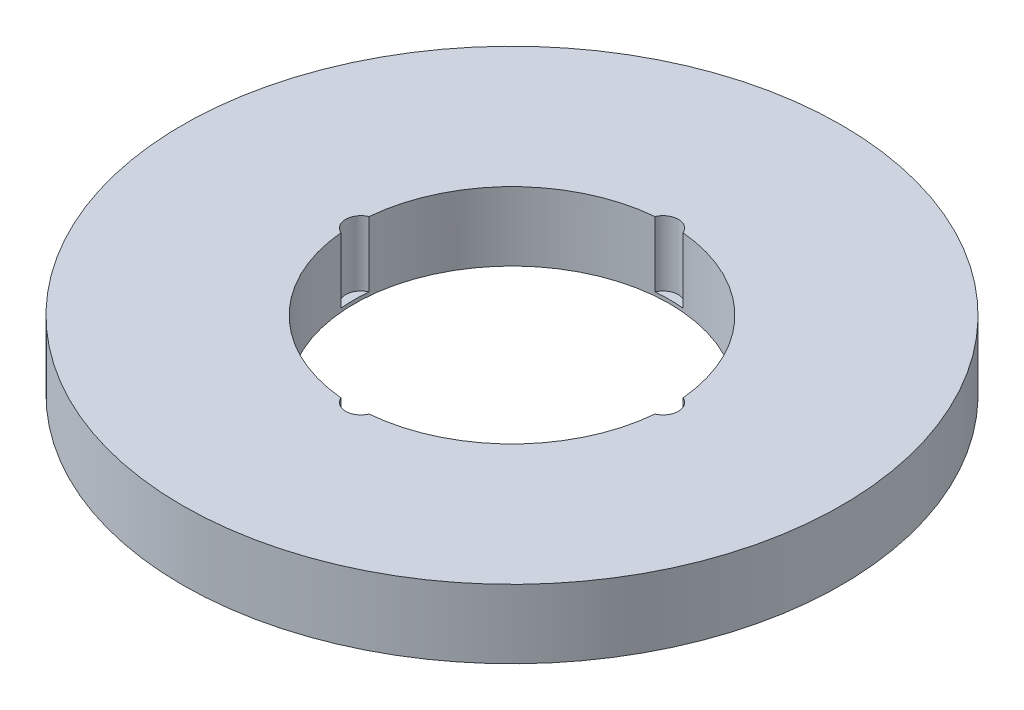
SolidWorks part; units mm, degrees
ref_plane "Front Plane" through (0, 0, 0) normal (0, 0, 1) x (1, 0, 0)
ref_plane "Top Plane" through (0, 0, 0) normal (0, 1, 0) x (1, 0, 0)
ref_plane "Right Plane" through (0, 0, 0) normal (1, 0, 0) x (0, 0, -1)
sketch "Sketch1" plane through (0, 0, 0) normal (0, 1, 0) x (1, 0, 0)
  circle A0 centre (0, 0) radius 57.5
  dimension "FLANGE_OD" = 115
extrude "Boss-Extrude1" add sketch "Sketch1" along normal blind 12
sketch "Sketch2" plane through (0, 0, 0) normal (0, 1, 0) x (1, 0, 0)
  circle A0 centre (0, 0) radius 27.5
  dimension "BORE_D" = 55
extrude "Cut-Extrude1" cut sketch "Sketch2" along normal through all
sketch "Sketch3" plane through (0, 12, 0) normal (0, 1, 0) x (1, 0, 0)
  circle A0 centre (0, 0) radius 26.3614 construction
  circle A1 centre (-26.3614, 0) radius 2.6565
  dimension "BOLT_D" = 5.3129
  dimension "BOLT_PCD" = 52.7228
extrude "Cut-Extrude2" cut sketch "Sketch3" against normal blind 11.3886
pattern_circular "CirPattern1" count 4 over 360 about axis through (0, 0, 0) along (0, 1, 0) of "Cut-Extrude2"
